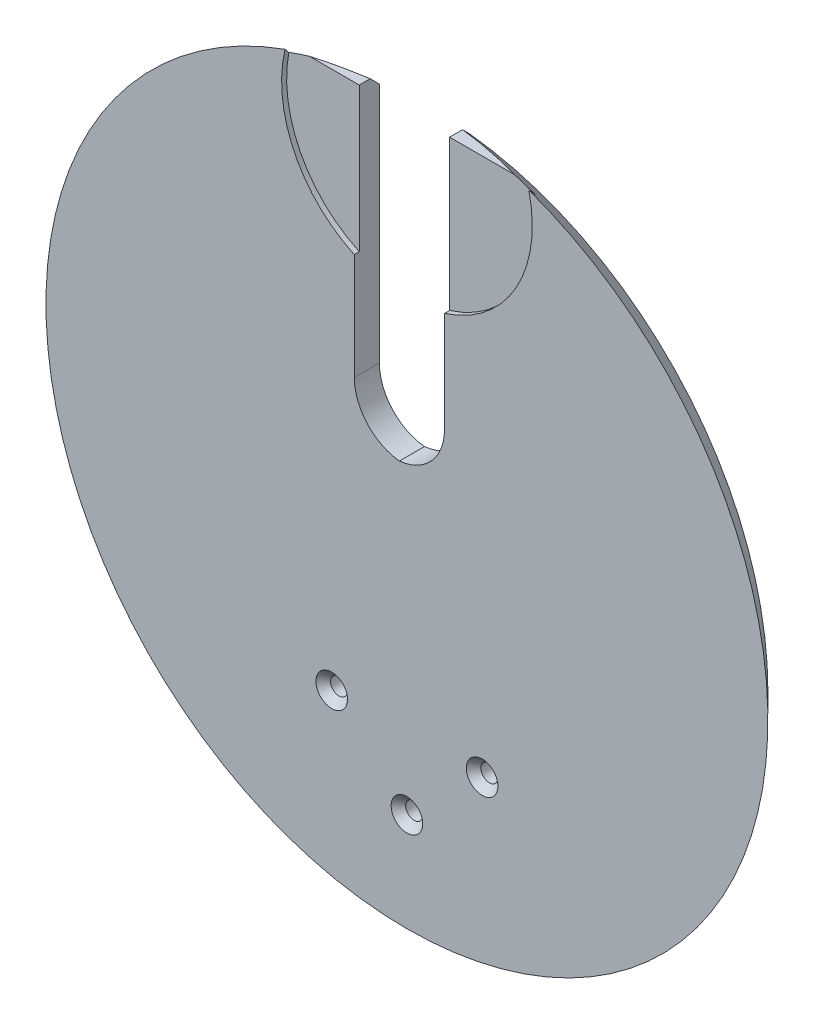
SolidWorks part; units mm, degrees
ref_plane "Front Plane" through (0, 0, 0) normal (0, 0, 1) x (1, 0, 0)
ref_plane "Top Plane" through (0, 0, 0) normal (0, 1, 0) x (1, 0, 0)
ref_plane "Right Plane" through (0, 0, 0) normal (1, 0, 0) x (0, 0, -1)
sketch "Sketch1" plane through (0, 0, 0) normal (0, 0, 1) x (1, 0, 0)
  line L0 (-9.944, -71.31) -> (9.944, -71.31) construction
  line L1 (-66.4124, -27.81) -> (66.4124, -27.81) construction
  line L2 (-35.1981, -62.81) -> (35.1981, -62.81) construction
  line L3 (0, -27.81) -> (0, -62.81) construction
  line L4 (-23.6643, 68) -> (23.6643, 68)
  arc A0 (-23.6643, 68) -> (23.6643, 68) centre (0, 0) ccw
  circle A1 centre (0, -52.31) radius 2.397 construction
  circle A2 centre (-15, -38.31) radius 2.5305 construction
  circle A3 centre (15, -38.31) radius 2.5603 construction
  arc A4 (23.6643, 68) -> (-23.6643, 68) centre (0, 0) ccw construction
  point P13 (0, -45.31)
  dimension "D1" = 144
  dimension "D2" = 71.31
  dimension "D3" = 43.5
  dimension "D4" = 35
  dimension "D5" = 7
  dimension "D6" = 15
  dimension "D7" = 15
  dimension "D8" = 7
  dimension "D9" = 68
extrude "Boss-Extrude2" add sketch "Sketch1" along normal blind 5 contours A0 L4
chamfer "Chamfer1" distance 5 angle 45 1 edges at (0, -72, 0)
sketch "Sketch2" plane through (0, 0, 5) normal (0, 0, 1) x (1, 0, 0)
  point P0 (15, -38.31)
  point P3 (-15, -38.31)
  point P6 (0, -52.31)
hole_wizard "CSK for M3 Countersunk Flat Head Screw1" positions "Sketch2" profile "Sketch3" countersink size "M3" standard "ISO"
sketch "Sketch3" plane through (15, -38.31, 5) normal (1, 0, 0) x (0, -1, 0)
  line L0 (0, 0) -> (0, 6.0215)
  line L1 (0, 6.0215) -> (1.7, 5)
  line L2 (1.7, 5) -> (1.7, 1.45)
  line L3 (1.7, 1.45) -> (3.15, 0)
  line L5 (3.15, 0) -> (0, 0)
  line L6 (-1.7, 1.45) -> (-3.15, 0) construction
  line L10 (0, 6.0215) -> (-1.7, 5) construction
  line L11 (0, -6.35) -> (0, 107.95) construction
  dimension "Hole Dia." = 3.4
  dimension "Hole Depth" = 5
  dimension "Near C'Sink Dia." = 6.3
  dimension "Near C'Sink Angle" = 90
  dimension "Drill Angle" = 118
sketch "Sketch4" plane through (0, 0, 5) normal (0, 0, 1) x (1, 0, 0)
  line L5 (23.6643, 68) -> (-23.6643, 68)
  line L6 (23.6643, 68) -> (-23.6643, 68)
  line L7 (-10.5, 8) -> (7.5, 8)
  line L8 (-10.5, 8) -> (-10.5, 68)
  line L9 (-10.5, 68) -> (7.5, 68)
  line L10 (7.5, 8) -> (7.5, 68)
  arc A2 (-23.6643, 68) -> (23.6643, 68) centre (0, 0) ccw
  arc A3 (-23.6643, 68) -> (23.6643, 68) centre (0, 0) ccw
  dimension "D1" = 60
  dimension "D2" = 7.5
  dimension "D3" = 18
  dimension "D4" = 0
extrude "Cut-Extrude1" cut sketch "Sketch4" against normal up to surface (5 mm away) contours L7 L10 L6 L8 region at (-1.5, 38, 5) up to face at (-13.3, -38.31, 0)
sketch "Sketch5" plane through (0, 0, 5) normal (0, 0, 1) x (1, 0, 0)
  circle A0 centre (0, 61.9) radius 25
  dimension "D1" = 50
  dimension "D2" = 61.9
extrude "Cut-Extrude2" cut sketch "Sketch5" against normal blind 1
fillet "Fillet1" radius 10 2 edges at (-10.5, 8, 2.5) (7.5, 8, 2.5)
